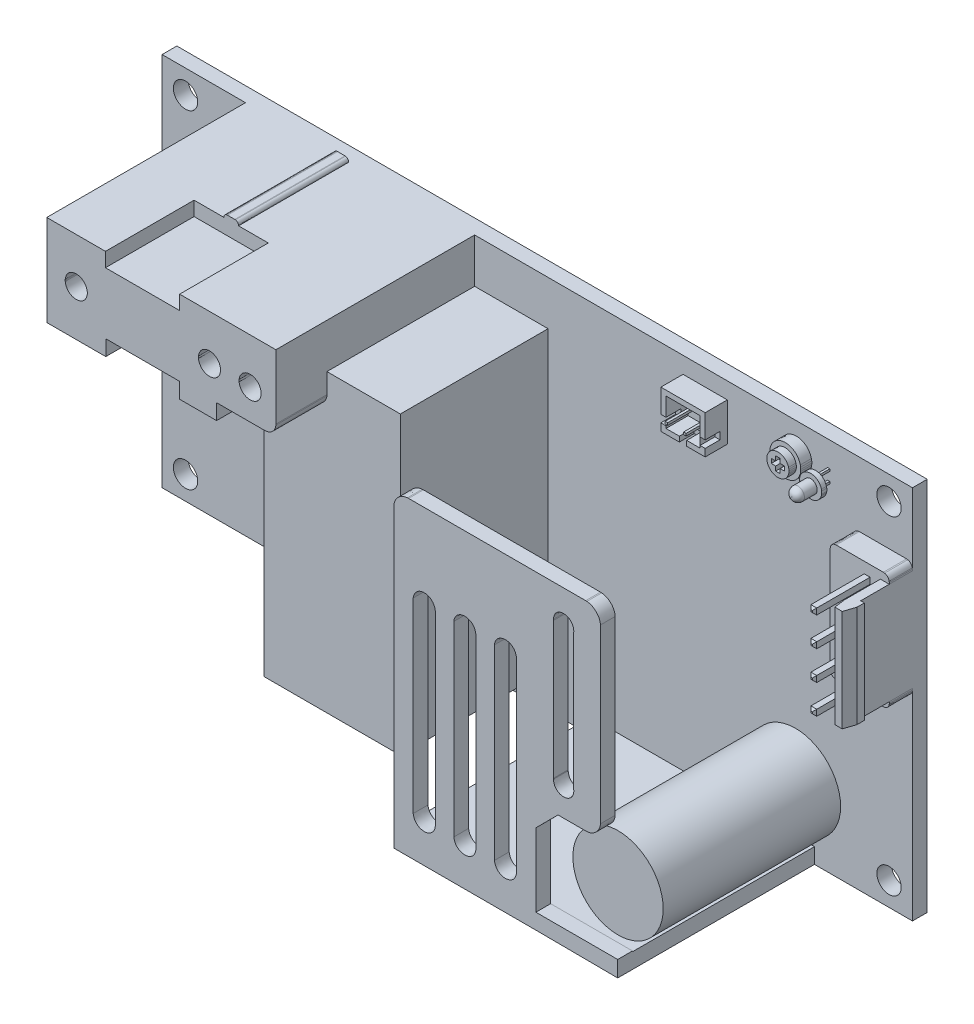
SolidWorks part; units mm, degrees
ref_plane "Спереди" through (0, 0, 0) normal (0, 0, 1) x (1, 0, 0)
ref_plane "Сверху" through (0, 0, 0) normal (0, 1, 0) x (1, 0, 0)
ref_plane "Справа" through (0, 0, 0) normal (1, 0, 0) x (0, 0, -1)
sketch "Model" plane through (0, 0, 0) normal (0, 0, 1) x (1, 0, 0)
  line L13 (0, 0) -> (101.6, 0)
  line L14 (0, 0) -> (0, 50.8)
  line L15 (0, 50.8) -> (101.6, 50.8)
  line L16 (101.6, 0) -> (101.6, 50.8)
  circle A5 centre (3.175, 47.625) radius 1.65
  circle A6 centre (3.175, 3.175) radius 1.65
  circle A7 centre (98.425, 3.175) radius 1.65
  circle A8 centre (98.425, 47.625) radius 1.65
  spline S9 degree 3 poles (101.6, 0.0137) (101.6, 0.0091) (101.6, 0.0046) (101.6, 0) knots 0 0 0 0 1 1 1 1 weights 1 1 1 1
  dimension "D1" = 101.6
  dimension "D3" = 3.175
  dimension "D4" = 44.45
  dimension "D5" = 3.175
  dimension "D6" = 95.25
  dimension "D7" = 3.3
  dimension "D2" = 50.8
extrude "Текстолит" add sketch "Model" against normal blind 2 contours L13 L16 L15 L14 A8 A7 A6 A5 region at (50.8, 25.4, 0)
sketch "Sketch2" plane through (0, 0, 0) normal (0, 0, 1) x (1, 0, 0)
  line L0 (0.0004, 28.8168) -> (1.197, 28.8168)
  line L1 (1.197, 28.8168) -> (1.197, 38.6355)
  line L2 (1.197, 38.6355) -> (0.0004, 38.6355)
  line L3 (0.0004, 38.6355) -> (0.0004, 38.8258)
  line L12 (0.0004, 28.8168) -> (0.0004, 28.6265)
  spline S0 degree 3 poles (7.1943, 27.8241) (7.2487, 27.8287) (7.3032, 27.8332) (7.3576, 27.8378) knots 15 15 15 15 16 16 16 16 weights 1 1 1 1
  spline S1 degree 3 poles (0.8028, 27.8241) (2.9333, 27.8241) (5.0638, 27.8241) (7.1943, 27.8241) knots 14 14 14 14 15 15 15 15 weights 1 1 1 1
  spline S2 degree 3 poles (0.6395, 27.8378) (0.6939, 27.8332) (0.7484, 27.8287) (0.8028, 27.8241) knots 13 13 13 13 14 14 14 14 weights 1 1 1 1
  spline S3 degree 3 poles (0.0141, 28.4632) (0.0547, 28.1742) (0.3505, 27.8784) (0.6395, 27.8378) knots 12 12 12 12 13 13 13 13 weights 1 1 1 1
  spline S4 degree 3 poles (0.0004, 28.6265) (0.0049, 28.5721) (0.0095, 28.5177) (0.0141, 28.4632) knots 11 11 11 11 12 12 12 12 weights 1 1 1 1
  spline S6 degree 3 poles (0.0141, 38.9891) (0.0095, 38.9346) (0.0049, 38.8802) (0.0004, 38.8258) knots 9 9 9 9 10 10 10 10 weights 1 1 1 1
  spline S7 degree 3 poles (0.6395, 39.6145) (0.3505, 39.5739) (0.0547, 39.2781) (0.0141, 38.9891) knots 8 8 8 8 9 9 9 9 weights 1 1 1 1
  spline S8 degree 3 poles (0.8028, 39.6282) (0.7484, 39.6236) (0.6939, 39.6191) (0.6395, 39.6145) knots 7 7 7 7 8 8 8 8 weights 1 1 1 1
  spline S9 degree 3 poles (7.1943, 39.6282) (5.0638, 39.6282) (2.9333, 39.6282) (0.8028, 39.6282) knots 6 6 6 6 7 7 7 7 weights 1 1 1 1
  spline S10 degree 3 poles (7.3576, 39.6145) (7.3032, 39.6191) (7.2487, 39.6236) (7.1943, 39.6282) knots 5 5 5 5 6 6 6 6 weights 1 1 1 1
  spline S11 degree 3 poles (7.9831, 38.9891) (7.942, 39.2777) (7.6466, 39.5743) (7.3576, 39.6145) knots 4 4 4 4 5 5 5 5 weights 1 1 1 1
  spline S12 degree 3 poles (7.9967, 38.8258) (7.9922, 38.8802) (7.9876, 38.9346) (7.9831, 38.9891) knots 3 3 3 3 4 4 4 4 weights 1 1 1 1
  spline S13 degree 3 poles (7.9967, 28.6265) (7.9967, 32.0263) (7.9967, 35.426) (7.9967, 38.8258) knots 2 2 2 2 3 3 3 3 weights 1 1 1 1
  spline S14 degree 3 poles (7.9831, 28.4632) (7.9876, 28.5177) (7.9922, 28.5721) (7.9967, 28.6265) knots 1 1 1 1 2 2 2 2 weights 1 1 1 1
  spline S15 degree 3 poles (7.3576, 27.8378) (7.6466, 27.8784) (7.942, 28.1742) (7.9831, 28.4632) knots 0 0 0 0 1 1 1 1 weights 1 1 1 1
sketch "Sketch3" plane through (0, 0, 0) normal (0, 0, 1) x (1, 0, 0)
  spline S0 degree 3 poles (13.6215, 24.7504) (13.617, 24.7504) (13.6124, 24.7504) (13.6079, 24.7504) (12.1121, 24.7504) (10.6162, 24.7504) (9.1204, 24.7504) knots 10 10 10 10 11 11 11 12 12 12 12 weights 1 1 1 1 1 1 1
  spline S1 degree 3 poles (13.6215, 33.2636) (13.6215, 33.2546) (13.6215, 33.2456) (13.6215, 33.2367) (13.6215, 30.4125) (13.6215, 27.5883) (13.6215, 24.7641) (13.6215, 24.7595) (13.6215, 24.755) (13.6215, 24.7504) knots 7 7 7 7 8 8 8 9 9 9 10 10 10 10 weights 1 1 1 1 1 1 1 1 1 1
  spline S2 degree 3 poles (9.1067, 33.2636) (9.1113, 33.2636) (9.1158, 33.2636) (9.1204, 33.2636) (10.6162, 33.2636) (12.1121, 33.2636) (13.6079, 33.2636) (13.6124, 33.2636) (13.617, 33.2636) (13.6215, 33.2636) knots 4 4 4 4 5 5 5 6 6 6 7 7 7 7 weights 1 1 1 1 1 1 1 1 1 1
  spline S3 degree 3 poles (9.1067, 24.7504) (9.1067, 24.755) (9.1067, 24.7595) (9.1067, 24.7641) (9.1067, 27.5883) (9.1067, 30.4125) (9.1067, 33.2367) (9.1067, 33.2456) (9.1067, 33.2546) (9.1067, 33.2636) knots 1 1 1 1 2 2 2 3 3 3 4 4 4 4 weights 1 1 1 1 1 1 1 1 1 1
  spline S4 degree 3 poles (9.1204, 24.7504) (9.1158, 24.7504) (9.1113, 24.7504) (9.1067, 24.7504) knots 0 0 0 0 1 1 1 1 weights 1 1 1 1
  spline S5 degree 3 poles (0.2313, 22.6162) (0.2399, 22.6162) (0.2489, 22.6162) (0.2578, 22.6162) (3.082, 22.6162) (5.9062, 22.6162) (8.7304, 22.6162) (8.735, 22.6162) (8.7395, 22.6162) (8.7444, 22.6162) knots 0 0 0 0 1 1 1 2 2 2 3 3 3 3 weights 1 1 1 1 1 1 1 1 1 1
  spline S6 degree 3 poles (8.7444, 27.1307) (8.7444, 27.1261) (8.7444, 27.1216) (8.7444, 27.117) (8.7444, 25.6212) (8.7444, 24.1254) (8.7444, 22.6295) (8.7444, 22.625) (8.7444, 22.6204) (8.7444, 22.6162) knots 6 6 6 6 7 7 7 8 8 8 9 9 9 9 weights 1 1 1 1 1 1 1 1 1 1
  spline S7 degree 3 poles (0.2313, 27.1307) (0.2403, 27.1307) (0.2492, 27.1307) (0.2582, 27.1307) (3.0824, 27.1307) (5.9066, 27.1307) (8.7308, 27.1307) (8.7353, 27.1307) (8.7399, 27.1307) (8.7444, 27.1307) knots 3 3 3 3 4 4 4 5 5 5 6 6 6 6 weights 1 1 1 1 1 1 1 1 1 1
  spline S8 degree 3 poles (0.2313, 22.6162) (0.2313, 22.6204) (0.2313, 22.625) (0.2313, 22.6295) (0.2313, 24.1254) (0.2313, 25.6212) (0.2313, 27.117) (0.2313, 27.1216) (0.2313, 27.1261) (0.2313, 27.1307) knots 0 0 0 0 1 1 1 2 2 2 3 3 3 3 weights 1 1 1 1 1 1 1 1 1 1
sketch "Sketch4" plane through (0, 0, 0) normal (0, 0, 1) x (1, 0, 0)
  line L0 (42.3183, 42.0829) -> (42.3183, 48.7752)
  line L1 (42.3183, 48.7752) -> (42.3183, 48.8758)
  line L2 (42.3183, 48.8758) -> (42.3183, 50.8)
  line L3 (11.295, 50.8) -> (11.295, 40.5823)
  line L5 (11.295, 50.8) -> (19.2847, 50.8)
  line L6 (0, 50.8) -> (101.6, 50.8) construction
  line L7 (11.2952, 40.4746) -> (11.295, 40.5823)
  line L8 (11.2952, 40.4746) -> (11.2952, 38.4749)
  line L9 (11.2952, 38.4749) -> (12.2902, 38.4749)
  line L10 (12.2902, 38.4749) -> (29.2842, 38.4749)
  line L11 (25.2637, 50.8) -> (42.3183, 50.8)
  line L12 (19.2847, 50.8) -> (23.2639, 50.8)
  line L14 (29.2842, 38.4749) -> (33.2841, 38.4749)
  line L15 (33.2841, 38.4749) -> (34.2889, 38.4749)
  line L16 (34.2889, 38.4749) -> (34.2889, 40.4746)
  line L17 (34.2889, 40.4746) -> (34.2889, 40.5753)
  line L18 (34.2889, 40.5753) -> (40.8213, 40.5753)
  line L24 (23.7663, 51.3024) -> (24.7612, 51.3024)
  line L30 (40.8213, 40.5753) -> (40.9619, 40.5851)
  line L31 (42.3187, 41.942) -> (42.3183, 42.0829)
  arc A0 (40.9619, 40.5851) -> (42.3187, 41.942) centre (40.8198, 42.084) ccw
  spline S0 degree 3 poles (23.2738, 50.8805) (23.2705, 50.8537) (23.2672, 50.8268) (23.2639, 50.8) knots 2 2 2 2 3 3 3 3 weights 1 1 1 1
  spline S1 degree 3 poles (23.6862, 51.2925) (23.4997, 51.2994) (23.2669, 51.0673) (23.2738, 50.8805) knots 1 1 1 1 2 2 2 2 weights 1 1 1 1
  spline S2 degree 3 poles (23.7663, 51.3024) (23.7396, 51.2994) (23.7129, 51.296) (23.6862, 51.2925) knots 0 0 0 0 1 1 1 1 weights 1 1 1 1
  spline S3 degree 3 poles (24.8418, 51.2925) (24.8149, 51.296) (24.7881, 51.2994) (24.7612, 51.3024) knots 2 2 2 2 3 3 3 3 weights 1 1 1 1
  spline S4 degree 3 poles (25.2538, 50.8805) (25.2261, 51.0761) (25.0464, 51.2906) (24.8418, 51.2925) knots 1 1 1 1 2 2 2 2 weights 1 1 1 1
  spline S5 degree 3 poles (25.2637, 50.8) (25.2604, 50.8268) (25.2571, 50.8537) (25.2538, 50.8805) knots 0 0 0 0 1 1 1 1 weights 1 1 1 1
  spline S6 degree 3 poles (37.3341, 44.8159) (37.3341, 44.7691) (37.3341, 44.7222) (37.3341, 44.6754) (37.3341, 44.6319) (37.3341, 44.5883) (37.3341, 44.5448) knots 4 4 4 4 5 5 5 6 6 6 6 weights 1 1 1 1 1 1 1
  spline S7 degree 3 poles (40.3189, 44.8159) (40.0873, 46.6281) (37.581, 46.633) (37.3341, 44.8159) knots 3 3 3 3 4 4 4 4 weights 1 1 1 1
  spline S8 degree 3 poles (40.3288, 44.6754) (40.3255, 44.7222) (40.3222, 44.7691) (40.3189, 44.8159) knots 2 2 2 2 3 3 3 3 weights 1 1 1 1
  spline S9 degree 3 poles (40.3189, 44.5448) (40.3222, 44.5883) (40.3255, 44.6319) (40.3288, 44.6754) knots 1 1 1 1 2 2 2 2 weights 1 1 1 1
  spline S10 degree 3 poles (37.3341, 44.5448) (37.5658, 42.7307) (40.0983, 42.7288) (40.3189, 44.5448) knots 0 0 0 0 1 1 1 1 weights 1 1 1 1
  spline S11 degree 3 poles (13.7875, 44.6754) (13.7908, 44.6319) (13.7941, 44.5883) (13.7974, 44.5448) knots 5 5 5 5 6 6 6 6 weights 1 1 1 1
  spline S12 degree 3 poles (13.7974, 44.8159) (13.7941, 44.7691) (13.7908, 44.7222) (13.7875, 44.6754) knots 4 4 4 4 5 5 5 5 weights 1 1 1 1
  spline S13 degree 3 poles (16.7826, 44.8159) (16.5365, 46.6311) (14.0309, 46.6303) (13.7974, 44.8159) knots 3 3 3 3 4 4 4 4 weights 1 1 1 1
  spline S14 degree 3 poles (16.7826, 44.5448) (16.7826, 44.5883) (16.7826, 44.6319) (16.7826, 44.6754) (16.7826, 44.7222) (16.7826, 44.7691) (16.7826, 44.8159) knots 1 1 1 1 2 2 2 3 3 3 3 weights 1 1 1 1 1 1 1
  spline S15 degree 3 poles (13.7974, 44.5448) (14.0184, 42.7288) (16.5505, 42.7307) (16.7826, 44.5448) knots 0 0 0 0 1 1 1 1 weights 1 1 1 1
  spline S16 degree 3 poles (31.8369, 44.8159) (31.8369, 44.7691) (31.8369, 44.7222) (31.8369, 44.6754) (31.8369, 44.6319) (31.8369, 44.5883) (31.8369, 44.5448) knots 4 4 4 4 5 5 5 6 6 6 6 weights 1 1 1 1 1 1 1
  spline S17 degree 3 poles (34.8217, 44.8159) (34.5893, 46.6292) (32.083, 46.6322) (31.8369, 44.8159) knots 3 3 3 3 4 4 4 4 weights 1 1 1 1
  spline S18 degree 3 poles (34.8316, 44.6754) (34.8283, 44.7222) (34.825, 44.7691) (34.8217, 44.8159) knots 2 2 2 2 3 3 3 3 weights 1 1 1 1
  spline S19 degree 3 poles (34.8217, 44.5448) (34.825, 44.5883) (34.8283, 44.6319) (34.8316, 44.6754) knots 1 1 1 1 2 2 2 2 weights 1 1 1 1
  spline S20 degree 3 poles (31.8369, 44.5448) (32.0685, 42.7307) (34.6011, 42.7288) (34.8217, 44.5448) knots 0 0 0 0 1 1 1 1 weights 1 1 1 1
  point P52 (24.2638, 50.8)
sketch "Sketch5" plane through (0, 0, 0) normal (0, 0, 1) x (1, 0, 0)
  line L0 (33.7672, 4.7598) -> (33.7865, 4.8384)
  line L5 (33.7865, 38.4749) -> (36.2891, 40.5753)
  line L6 (42.3187, 44.7825) -> (36.2891, 40.5753)
  spline S0 degree 3 poles (52.2616, 4.7598) (52.2616, 4.7647) (52.2616, 4.7693) (52.2616, 4.7738) (52.2616, 18.1056) (52.2616, 31.4374) (52.2616, 44.7692) (52.2616, 44.7738) (52.2616, 44.7783) (52.2616, 44.7825) knots 0 0 0 0 1 1 1 2 2 2 3 3 3 3 weights 1 1 1 1 1 1 1 1 1 1
  spline S1 degree 3 poles (42.3187, 44.7825) (42.9246, 44.7825) (43.5306, 44.7825) (44.1365, 44.7825) (46.8403, 44.7825) (49.5445, 44.7825) (52.2487, 44.7825) (52.2531, 44.7825) (52.2576, 44.7825) (52.2616, 44.7825) knots 0 0 0 0 1 1 1 2 2 2 3 3 3 3 weights 1 1 1 1 1 1 1 1 1 1
  spline S2 degree 3 poles (33.7672, 4.7598) (33.7717, 4.7598) (33.7763, 4.7598) (33.7808, 4.7598) (39.9365, 4.7598) (46.0926, 4.7598) (52.2483, 4.7598) (52.2529, 4.7598) (52.2574, 4.7598) (52.2616, 4.7598) knots 0 0 0 0 1 1 1 2 2 2 3 3 3 3 weights 1 1 1 1 1 1 1 1 1 1
  spline S5 degree 3 poles (33.7865, 38.4749) (33.7865, 38.2539) (33.7865, 38.0329) (33.7865, 37.8118) (33.7865, 26.8239) (33.7865, 15.8362) (33.7865, 4.8486) (33.7865, 4.8452) (33.7865, 4.8418) (33.7865, 4.8384) knots 3 3 3 3 4 4 4 5 5 5 6 6 6 6 weights 1 1 1 1 1 1 1 1 1 1
  spline S6 degree 3 poles (33.7865, 4.8384) (33.7865, 4.8417) (33.7865, 4.8449) (33.7865, 4.8482) (33.7865, 15.8093) (33.7865, 26.7703) (33.7865, 37.7313) (33.7865, 37.9792) (33.7865, 38.227) (33.7865, 38.4749) knots 0 0 0 0 1 1 1 2 2 2 3 3 3 3 weights 1 1 1 1 1 1 1 1 1 1
sketch "Sketch6" plane through (0, 0, 0) normal (0, 0, 1) x (1, 0, 0)
  line L0 (70.5328, 48.5697) -> (76.5302, 48.5697)
  line L1 (76.5302, 48.5697) -> (76.5302, 43.3748)
  line L2 (70.5328, 43.3748) -> (73.035, 43.3752)
  line L3 (70.5328, 43.3748) -> (70.5328, 48.5697)
  line L4 (73.035, 44.0686) -> (74.028, 44.0686)
  line L5 (73.035, 44.0686) -> (71.2266, 44.0686)
  line L6 (71.2266, 44.0686) -> (71.2266, 47.8763)
  line L7 (71.2266, 47.8763) -> (72.5318, 47.8763)
  line L8 (72.5318, 47.8763) -> (75.8364, 47.8763)
  line L9 (75.8364, 47.8763) -> (75.8364, 44.0686)
  line L10 (75.8364, 44.0686) -> (74.028, 44.0686)
  line L11 (74.028, 43.3752) -> (73.035, 43.3752)
  line L12 (74.028, 43.3752) -> (76.5302, 43.3748)
sketch "Sketch8" plane through (0, 0, 0) normal (0, 0, 1) x (1, 0, 0)
  spline S0 degree 3 poles (91.7546, 46.3463) (91.7409, 46.2828) (91.7273, 46.2192) (91.7136, 46.1557) knots 7 7 7 7 8 8 8 8 weights 1 1 1 1
  spline S1 degree 3 poles (91.7546, 46.7268) (91.7546, 46.6634) (91.7546, 46.6) (91.7546, 46.5366) (91.7546, 46.4731) (91.7546, 46.4097) (91.7546, 46.3463) knots 5 5 5 5 6 6 6 7 7 7 7 weights 1 1 1 1 1 1 1
  spline S2 degree 3 poles (91.7136, 46.9038) (91.7273, 46.8448) (91.7409, 46.7858) (91.7546, 46.7268) knots 4 4 4 4 5 5 5 5 weights 1 1 1 1
  spline S3 degree 3 poles (88.8173, 46.9854) (89.3394, 48.4296) (91.2974, 48.3685) (91.7136, 46.9038) knots 3 3 3 3 4 4 4 4 weights 1 1 1 1
  spline S4 degree 3 poles (88.7763, 46.7952) (88.7899, 46.8586) (88.8036, 46.922) (88.8173, 46.9854) knots 2 2 2 2 3 3 3 3 weights 1 1 1 1
  spline S5 degree 3 poles (88.7626, 46.6182) (88.7671, 46.6772) (88.7717, 46.7362) (88.7763, 46.7952) knots 1 1 1 1 2 2 2 2 weights 1 1 1 1
  spline S6 degree 3 poles (91.7136, 46.1557) (91.1808, 44.3944) (88.7083, 44.8284) (88.7626, 46.6182) knots 0 0 0 0 1 1 1 1 weights 1 1 1 1
sketch "Sketch9" plane through (0, 0, 0) normal (0, 0, 1) x (1, 0, 0)
  line L0 (101.6, 27.2799) -> (100.4033, 27.2799)
  line L1 (100.4033, 27.2799) -> (100.4033, 41.056)
  line L2 (100.4033, 41.056) -> (101.6, 41.056)
  line L3 (101.6003, 27.0897) -> (101.6, 27.2799)
  line L20 (101.6, 41.056) -> (101.6003, 41.26)
  spline S0 degree 3 poles (94.2431, 26.3009) (94.2975, 26.2964) (94.352, 26.2918) (94.406, 26.2873) knots 3 3 3 3 4 4 4 4 weights 1 1 1 1
  spline S1 degree 3 poles (93.6177, 26.9264) (93.6587, 26.637) (93.9537, 26.3416) (94.2431, 26.3009) knots 2 2 2 2 3 3 3 3 weights 1 1 1 1
  spline S2 degree 3 poles (93.604, 27.0897) (93.6085, 27.0352) (93.6131, 26.9808) (93.6177, 26.9264) knots 1 1 1 1 2 2 2 2 weights 1 1 1 1
  spline S3 degree 3 poles (93.604, 41.26) (93.604, 36.5368) (93.604, 31.8132) (93.604, 27.0897) knots 0 0 0 0 1 1 1 1 weights 1 1 1 1
  spline S4 degree 3 poles (93.6177, 41.4096) (93.6131, 41.3597) (93.6085, 41.3098) (93.604, 41.26) knots 3 3 3 3 4 4 4 4 weights 1 1 1 1
  spline S5 degree 3 poles (94.2435, 42.0354) (93.9431, 42.0054) (93.661, 41.6898) (93.6177, 41.4096) knots 2 2 2 2 3 3 3 3 weights 1 1 1 1
  spline S6 degree 3 poles (94.4064, 42.0624) (94.3521, 42.0534) (94.2978, 42.0444) (94.2435, 42.0354) knots 1 1 1 1 2 2 2 2 weights 1 1 1 1
  spline S7 degree 3 poles (100.7979, 42.0624) (98.6677, 42.0624) (96.537, 42.0624) (94.4064, 42.0624) knots 0 0 0 0 1 1 1 1 weights 1 1 1 1
  spline S8 degree 3 poles (100.9612, 42.035) (100.9068, 42.0441) (100.8524, 42.0533) (100.7979, 42.0624) knots 3 3 3 3 4 4 4 4 weights 1 1 1 1
  spline S9 degree 3 poles (101.5867, 41.4096) (101.5445, 41.6891) (101.2608, 42.0058) (100.9612, 42.035) knots 2 2 2 2 3 3 3 3 weights 1 1 1 1
  spline S10 degree 3 poles (101.6003, 41.26) (101.5958, 41.3098) (101.5912, 41.3597) (101.5867, 41.4096) knots 1 1 1 1 2 2 2 2 weights 1 1 1 1
  spline S12 degree 3 poles (101.5867, 26.9264) (101.5912, 26.9808) (101.5958, 27.0352) (101.6003, 27.0897) knots 3 3 3 3 4 4 4 4 weights 1 1 1 1
  spline S13 degree 3 poles (100.9612, 26.3009) (101.2498, 26.3416) (101.546, 26.6374) (101.5867, 26.9264) knots 2 2 2 2 3 3 3 3 weights 1 1 1 1
  spline S14 degree 3 poles (100.7979, 26.2873) (100.8524, 26.2918) (100.9068, 26.2964) (100.9612, 26.3009) knots 1 1 1 1 2 2 2 2 weights 1 1 1 1
  spline S15 degree 3 poles (94.406, 26.2873) (96.5367, 26.2873) (98.6673, 26.2873) (100.7979, 26.2873) knots 0 0 0 0 1 1 1 1 weights 1 1 1 1
sketch "Sketch10" plane through (0, 0, 0) normal (0, 0, 1) x (1, 0, 0)
  circle A0 centre (85.7534, 8.5646) radius 6.1168
sketch "Sketch12" plane through (0, 0, 0) normal (0, 0, 1) x (1, 0, 0)
  line L0 (66.1368, 30.5761) -> (66.1368, 5.5823)
  line L1 (83.9949, 15.0783) -> (80.2464, 15.0783)
  line L2 (80.2464, 15.0783) -> (77.2517, 12.0729)
  line L3 (60.0165, 42.0817) -> (83.9949, 42.0817)
  line L4 (74.6288, 5.5804) -> (74.6288, 30.5746)
  line L5 (79.6335, 37.5794) -> (79.6335, 19.0774)
  line L6 (69.1315, 5.5808) -> (69.1315, 30.5746)
  line L7 (71.6337, 30.5746) -> (71.6337, 5.5804)
  line L8 (85.995, 40.082) -> (85.995, 17.078)
  line L9 (77.2517, 2.1741) -> (77.2517, 12.0729)
  line L11 (77.2517, 0.0737) -> (58.0167, 0.0752)
  line L12 (59.8558, 42.073) -> (60.0165, 42.0817)
  line L13 (83.9949, 42.0817) -> (84.1559, 42.0715)
  line L14 (85.995, 40.2324) -> (85.995, 40.082)
  line L15 (85.995, 17.078) -> (85.995, 16.9166)
  line L16 (84.1555, 15.0874) -> (83.9949, 15.0783)
  line L17 (66.1368, 5.4403) -> (66.1368, 5.5823)
  line L18 (69.1217, 5.4403) -> (69.1315, 5.5808)
  line L19 (66.1368, 30.7151) -> (66.1368, 30.5761)
  line L20 (69.1217, 30.7151) -> (69.1315, 30.5746)
  line L21 (77.2517, 2.1741) -> (88.3281, 2.1741)
  line L22 (88.3281, 2.1741) -> (88.3281, 0)
  line L23 (0, 0) -> (101.6, 0) construction
  line L24 (88.3281, 0) -> (77.2517, 0.0737)
  spline S0 degree 3 poles (60.6396, 30.7166) (60.6396, 30.6698) (60.6396, 30.623) (60.6396, 30.5761) (60.6396, 22.2449) (60.6396, 13.9136) (60.6396, 5.5823) (60.6396, 5.5355) (60.6396, 5.4886) (60.6396, 5.4418) knots 5 5 5 5 6 6 6 7 7 7 8 8 8 8 weights 1 1 1 1 1 1 1 1 1 1
  spline S1 degree 3 poles (63.6343, 30.7166) (63.3814, 32.5292) (60.8906, 32.533) (60.6396, 30.7166) knots 4 4 4 4 5 5 5 5 weights 1 1 1 1
  spline S2 degree 3 poles (63.6343, 5.4418) (63.6343, 5.4886) (63.6343, 5.5355) (63.6343, 5.5823) (63.6343, 13.9136) (63.6343, 22.2449) (63.6343, 30.5761) (63.6343, 30.623) (63.6343, 30.6698) (63.6343, 30.7166) knots 1 1 1 1 2 2 2 3 3 3 4 4 4 4 weights 1 1 1 1 1 1 1 1 1 1
  spline S3 degree 3 poles (60.6396, 5.4418) (60.8868, 3.6251) (63.386, 3.6292) (63.6343, 5.4418) knots 0 0 0 0 1 1 1 1 weights 1 1 1 1
  spline S4 degree 3 poles (58.0167, 40.2339) (58.0167, 40.1836) (58.0167, 40.1334) (58.0167, 40.0831) (58.0167, 27.4473) (58.0167, 14.8114) (58.0167, 2.1756) (58.0167, 2.1422) (58.0167, 2.1087) (58.0167, 2.0753) (58.0167, 1.4086) (58.0167, 0.7419) (58.0167, 0.0752) knots 2 2 2 2 3 3 3 4 4 4 5 5 5 6 6 6 6 weights 1 1 1 1 1 1 1 1 1 1 1 1 1
  spline S5 degree 3 poles (59.8558, 42.073) (58.8916, 42.0103) (58.0801, 41.1977) (58.0167, 40.2339) knots 1 1 1 1 2 2 2 2 weights 1 1 1 1
  spline S9 degree 3 poles (66.1368, 5.4403) (66.3598, 3.6308) (68.9109, 3.6296) (69.1217, 5.4403) knots 1 1 1 1 2 2 2 2 weights 1 1 1 1
  spline S12 degree 3 poles (69.1217, 30.7151) (68.9079, 32.5254) (66.362, 32.5235) (66.1368, 30.7151) knots 1 1 1 1 2 2 2 2 weights 1 1 1 1
  spline S14 degree 3 poles (71.6337, 30.7151) (71.6337, 30.6683) (71.6337, 30.6215) (71.6337, 30.5746) knots 2 2 2 2 3 3 3 3 weights 1 1 1 1
  spline S15 degree 3 poles (74.6189, 30.7151) (74.4047, 32.5254) (71.8596, 32.5239) (71.6337, 30.7151) knots 1 1 1 1 2 2 2 2 weights 1 1 1 1
  spline S16 degree 3 poles (74.6288, 30.5746) (74.6255, 30.6215) (74.6222, 30.6683) (74.6189, 30.7151) knots 0 0 0 0 1 1 1 1 weights 1 1 1 1
  spline S17 degree 3 poles (79.6236, 37.7097) (79.627, 37.6662) (79.6304, 37.6226) (79.6335, 37.5794) knots 3 3 3 3 4 4 4 4 weights 1 1 1 1
  spline S18 degree 3 poles (82.3874, 37.7097) (82.2765, 39.5359) (79.7333, 39.5291) (79.6236, 37.7097) knots 2 2 2 2 3 3 3 3 weights 1 1 1 1
  spline S19 degree 3 poles (82.3771, 37.5791) (82.3805, 37.6226) (82.384, 37.6662) (82.3874, 37.7097) knots 1 1 1 1 2 2 2 2 weights 1 1 1 1
  spline S20 degree 3 poles (82.3768, 19.0774) (82.3771, 25.2449) (82.3771, 31.412) (82.3771, 37.5791) knots 0 0 0 0 1 1 1 1 weights 1 1 1 1
  spline S22 degree 3 poles (85.995, 40.2324) (85.9361, 41.1886) (85.114, 42.016) (84.1559, 42.0715) knots 1 1 1 1 2 2 2 2 weights 1 1 1 1
  spline S24 degree 3 poles (82.387, 18.9467) (82.3836, 18.9903) (82.3802, 19.0338) (82.3768, 19.0774) knots 2 2 2 2 3 3 3 3 weights 1 1 1 1
  spline S25 degree 3 poles (79.6232, 18.9467) (79.7333, 17.1274) (82.2761, 17.1205) (82.387, 18.9467) knots 1 1 1 1 2 2 2 2 weights 1 1 1 1
  spline S26 degree 3 poles (79.6335, 19.0774) (79.63, 19.0338) (79.6266, 18.9903) (79.6232, 18.9467) knots 0 0 0 0 1 1 1 1 weights 1 1 1 1
  spline S28 degree 3 poles (84.1555, 15.0874) (85.1128, 15.1341) (85.9289, 15.9657) (85.995, 16.9166) knots 1 1 1 1 2 2 2 2 weights 1 1 1 1
  spline S30 degree 3 poles (74.6185, 5.4399) (74.6219, 5.4867) (74.6253, 5.5336) (74.6288, 5.5804) knots 2 2 2 2 3 3 3 3 weights 1 1 1 1
  spline S31 degree 3 poles (71.6337, 5.4399) (71.8574, 3.63) (74.4074, 3.6292) (74.6185, 5.4399) knots 1 1 1 1 2 2 2 2 weights 1 1 1 1
  spline S32 degree 3 poles (71.6337, 5.5804) (71.6337, 5.5336) (71.6337, 5.4867) (71.6337, 5.4399) knots 0 0 0 0 1 1 1 1 weights 1 1 1 1
extrude "Предохранители" add sketch "Sketch3" along normal blind 8
sketch "Sketch13" plane through (0, 0, 0) normal (0, 0, 1) x (1, 0, 0)
  spline S0 degree 3 poles (87.9602, 47.1491) (87.9466, 47.2306) (87.9331, 47.3121) (87.9195, 47.3936) knots 7 7 7 7 8 8 8 8 weights 1 1 1 1
  spline S1 degree 3 poles (87.9739, 46.8905) (87.9693, 46.9767) (87.9647, 47.0629) (87.9602, 47.1491) knots 6 6 6 6 7 7 7 7 weights 1 1 1 1
  spline S2 degree 3 poles (87.9602, 46.6459) (87.9647, 46.7274) (87.9693, 46.809) (87.9739, 46.8905) knots 5 5 5 5 6 6 6 6 weights 1 1 1 1
  spline S3 degree 3 poles (87.9195, 46.3873) (87.9331, 46.4735) (87.9466, 46.5597) (87.9602, 46.6459) knots 4 4 4 4 5 5 5 5 weights 1 1 1 1
  spline S4 degree 3 poles (83.7989, 46.6459) (84.1061, 44.3276) (87.3154, 44.1331) (87.9195, 46.3873) knots 3 3 3 3 4 4 4 4 weights 1 1 1 1
  spline S5 degree 3 poles (83.7852, 46.8905) (83.7898, 46.809) (83.7943, 46.7274) (83.7989, 46.6459) knots 2 2 2 2 3 3 3 3 weights 1 1 1 1
  spline S6 degree 3 poles (83.7989, 47.1491) (83.7943, 47.0629) (83.7898, 46.9767) (83.7852, 46.8905) knots 1 1 1 1 2 2 2 2 weights 1 1 1 1
  spline S7 degree 3 poles (87.9195, 47.3936) (87.2983, 49.6558) (84.1411, 49.469) (83.7989, 47.1491) knots 0 0 0 0 1 1 1 1 weights 1 1 1 1
extrude "подстройка няпряжения-1" add sketch "Sketch13" along normal blind 1.5
sketch "Sketch7" plane through (0, 0, 0) normal (0, 0, 1) x (1, 0, 0)
  line L0 (85.5807, 47.7878) -> (85.5807, 47.1893)
  line L1 (85.5807, 47.1893) -> (84.9822, 47.1893)
  line L2 (84.9822, 47.1893) -> (84.9822, 46.5912)
  line L3 (84.9822, 46.5912) -> (85.5807, 46.5912)
  line L4 (85.5807, 46.5912) -> (85.5807, 45.9928)
  line L5 (85.5807, 45.9928) -> (86.1792, 45.9928)
  line L6 (86.1792, 45.9928) -> (86.1792, 46.5912)
  line L7 (86.1792, 46.5912) -> (86.7773, 46.5912)
  line L8 (86.7773, 46.5912) -> (86.7773, 47.1893)
  line L9 (86.7773, 47.1893) -> (86.1792, 47.1893)
  line L10 (86.1792, 47.1893) -> (86.1792, 47.7878)
  line L11 (86.1792, 47.7878) -> (85.5807, 47.7878)
  spline S8 degree 3 poles (87.3621, 47.1081) (87.3485, 47.176) (87.335, 47.244) (87.3214, 47.312) knots 7 7 7 7 8 8 8 8 weights 1 1 1 1
  spline S9 degree 3 poles (87.3757, 46.8905) (87.3712, 46.963) (87.3666, 47.0355) (87.3621, 47.1081) knots 6 6 6 6 7 7 7 7 weights 1 1 1 1
  spline S10 degree 3 poles (87.3621, 46.6729) (87.3666, 46.7454) (87.3712, 46.8179) (87.3757, 46.8905) knots 5 5 5 5 6 6 6 6 weights 1 1 1 1
  spline S11 degree 3 poles (87.3214, 46.469) (87.335, 46.5369) (87.3485, 46.6049) (87.3621, 46.6729) knots 4 4 4 4 5 5 5 5 weights 1 1 1 1
  spline S12 degree 3 poles (84.3974, 46.6729) (84.6723, 45.081) (86.8206, 44.9317) (87.3214, 46.469) knots 3 3 3 3 4 4 4 4 weights 1 1 1 1
  spline S13 degree 3 poles (84.3841, 46.8905) (84.3885, 46.8179) (84.393, 46.7454) (84.3974, 46.6729) knots 2 2 2 2 3 3 3 3 weights 1 1 1 1
  spline S14 degree 3 poles (84.3974, 47.1081) (84.393, 47.0355) (84.3885, 46.963) (84.3841, 46.8905) knots 1 1 1 1 2 2 2 2 weights 1 1 1 1
  spline S15 degree 3 poles (87.3214, 47.312) (86.8221, 48.8579) (84.6708, 48.7064) (84.3974, 47.1081) knots 0 0 0 0 1 1 1 1 weights 1 1 1 1
extrude "подстройка няпряжения-2" add sketch "Sketch7" along normal blind 2.5
extrude "светодиод-1" add sketch "Sketch8" along normal blind 0.68 from offset 1.76 separate body
sketch "Sketch14" plane through (0, 0, 2.44) normal (0, 0, 1) x (1, 0, 0)
  line L0 (90.2582, 45.0344) -> (90.2582, 48.0387) construction
  line L1 (88.7619, 46.5366) -> (91.7546, 46.5366) construction
  line L2 (91.7546, 46.3463) -> (91.7546, 46.7268) construction
  line L4 (90.1082, 47.4266) -> (90.4082, 47.4266)
  line L5 (90.1082, 47.4266) -> (90.1082, 47.1266)
  line L6 (90.1082, 47.1266) -> (90.4082, 47.1266)
  line L7 (90.4082, 47.4266) -> (90.4082, 47.1266)
  line L8 (90.1082, 47.4266) -> (90.4082, 47.1266) construction
  line L9 (90.1082, 47.1266) -> (90.4082, 47.4266) construction
  line L10 (90.1082, 45.6466) -> (90.4082, 45.6466)
  line L11 (90.1082, 45.6466) -> (90.1082, 45.9466)
  line L12 (90.1082, 45.9466) -> (90.4082, 45.9466)
  line L13 (90.4082, 45.6466) -> (90.4082, 45.9466)
  line L14 (90.1082, 45.6466) -> (90.4082, 45.9466) construction
  line L15 (90.1082, 45.9466) -> (90.4082, 45.6466) construction
  spline S2 degree 3 poles (88.7626, 46.6182) (88.7083, 44.8284) (91.1808, 44.3944) (91.7136, 46.1557) knots 0 0 0 0 1 1 1 1 weights 1 1 1 1 construction
  point P2 (90.2582, 47.2766)
  point P11 (90.2582, 46.5366)
  point P15 (90.2582, 45.7966)
  dimension "D1" = 0.3
  dimension "D2" = 1.48
  dimension "D3" = 0.74
extrude "светодиод-ноги" add sketch "Sketch14" against normal blind 6.02
sketch "Sketch15" plane through (0, 0, 2.44) normal (0, 0, 1) x (1, 0, 0)
  circle A0 centre (90.2582, 46.5366) radius 0.885
  dimension "D1" = 1.77
extrude "светодиод-2" add sketch "Sketch15" along normal blind 2.56
fillet "светодиод-3" radius 0.83 1 edges at (91.1432, 46.5366, 5)
sketch "Sketch16" plane through (0, 0, 0) normal (0, 0, 1) x (1, 0, 0)
  line L0 (2.6043, 38.1525) -> (3.393, 38.1525)
  line L1 (3.393, 38.1525) -> (3.393, 37.3234)
  line L2 (3.393, 37.3234) -> (2.6043, 37.3234)
  line L3 (2.6043, 37.3234) -> (2.6043, 38.1525)
  line L4 (2.6043, 30.122) -> (3.393, 30.122)
  line L5 (3.393, 30.122) -> (3.393, 29.293)
  line L6 (3.393, 29.293) -> (2.6043, 29.293)
  line L7 (2.6043, 29.293) -> (2.6043, 30.122)
extrude "CN1 ввод" add sketch "Sketch2" along normal blind 3.27
extrude "CN1 ноги" add sketch "Sketch16" along normal blind 10.8
sketch "Sketch17" plane through (0, 28.8168, 0) normal (0, 1, 0) x (1, 0, 0)
  line L1 (0, 0) -> (1.2, 0)
  line L2 (0, 0) -> (0, -7)
  line L3 (0, -9.51) -> (1, -9.51)
  line L4 (1.2, 0) -> (1.2, -8)
  line L5 (0, -7) -> (-0.5, -7)
  line L6 (-0.5, -7) -> (-0.5, -8)
  line L7 (-0.5, -8) -> (0, -9.51)
  line L8 (1.2, -8) -> (1, -9.51)
  dimension "D1" = 9.51
  dimension "D2" = 0.5
  dimension "D3" = 7
  dimension "D4" = 8
  dimension "D5" = 1
  dimension "D6" = 0.5
  dimension "D7" = 1.7
extrude "CN1 зацеп" add sketch "Sketch17" along normal up to surface (9.8188 mm away) up to face at (0.5987, 38.6355, 1.635)
chamfer "CN1 ногих45" distance 0.3 angle 45 8 edges at (3.393, 29.7075, 10.8) (2.9987, 30.122, 10.8) (2.6043, 29.7075, 10.8) (2.9987, 29.293, 10.8) (3.393, 37.738, 10.8) (2.9987, 38.1525, 10.8) (2.6043, 37.738, 10.8) (2.9987, 37.3234, 10.8)
sketch "Sketch18" plane through (0, 0, 0) normal (0, 0, 1) x (1, 0, 0)
  line L0 (98.2073, 40.5798) -> (98.9961, 40.5798)
  line L1 (98.9961, 40.5798) -> (98.9961, 39.7509)
  line L2 (98.9961, 39.7509) -> (98.2073, 39.7509)
  line L3 (98.2073, 39.7509) -> (98.2073, 40.5798)
  line L4 (98.2073, 36.6232) -> (98.9961, 36.6232)
  line L5 (98.9961, 36.6232) -> (98.9961, 35.7942)
  line L6 (98.9961, 35.7942) -> (98.2073, 35.7942)
  line L7 (98.2073, 35.7942) -> (98.2073, 36.6232)
  line L8 (98.2073, 32.6663) -> (98.9961, 32.6663)
  line L9 (98.9961, 32.6663) -> (98.9961, 31.8372)
  line L10 (98.9961, 31.8372) -> (98.2073, 31.8372)
  line L11 (98.2073, 31.8372) -> (98.2073, 32.6663)
  line L12 (98.2073, 28.7093) -> (98.9961, 28.7093)
  line L13 (98.9961, 28.7093) -> (98.9961, 27.8803)
  line L14 (98.9961, 27.8803) -> (98.2073, 27.8803)
  line L15 (98.2073, 27.8803) -> (98.2073, 28.7093)
extrude "CN2 вывод" add sketch "Sketch9" along normal blind 3.14
extrude "CN2 ноги" add sketch "Sketch18" along normal blind 10.66
chamfer "CN2 ногих45" distance 0.3 angle 45 16 edges at (98.6017, 28.7093, 10.66) (98.2073, 28.2948, 10.66) (98.6017, 27.8803, 10.66) (98.9961, 28.2948, 10.66) (98.9961, 32.2517, 10.66) (98.6017, 31.8372, 10.66) (98.2073, 32.2517, 10.66) (98.6017, 32.6663, 10.66) (98.2073, 36.2087, 10.66) (98.6017, 35.7942, 10.66) (98.6017, 36.6232, 10.66) (98.9961, 36.2087, 10.66) (98.2073, 40.1654, 10.66) (98.6017, 40.5798, 10.66) (98.9961, 40.1654, 10.66) (98.6017, 39.7509, 10.66)
sketch "Sketch19" plane through (0, 41.056, 0) normal (0, -1, 0) x (1, 0, 0)
  line L0 (101.6, 7.01) -> (102.1, 7.01)
  line L1 (101.6, 0) -> (100.4, 0)
  line L2 (101.6, 0) -> (101.6, 7.01)
  line L3 (101.6, 9.51) -> (100.6, 9.51)
  line L4 (100.4, 0) -> (100.4, 8.01)
  line L5 (102.1, 7.01) -> (102.1, 8.01)
  line L6 (102.1, 8.01) -> (101.6, 9.51)
  line L7 (100.6, 9.51) -> (100.4, 8.01)
  line L8 (100.7979, 0) -> (94.406, 0) construction
  dimension "D1" = 9.51
  dimension "D2" = 1.2
  dimension "D3" = 0.5
  dimension "D4" = 2.5
  dimension "D5" = 1
  dimension "D6" = 1.5
  dimension "D7" = 1
extrude "CN2 зацеп" add sketch "Sketch19" along normal up to surface (13.7761 mm away) up to face at (101.0016, 27.2799, 1.57)
extrude "CN101 ввод" add sketch "Sketch6" along normal blind 3
sketch "Sketch20" plane through (0, 0, 0) normal (0, 0, 1) x (1, 0, 0)
  line L0 (72.4528, 45.5348) -> (72.1186, 45.5348)
  line L1 (72.1186, 45.5348) -> (72.1186, 45.8528)
  line L2 (72.1186, 45.8528) -> (72.4528, 45.8528)
  line L3 (72.4528, 45.8528) -> (72.4528, 45.5348)
  line L4 (74.9496, 45.5348) -> (74.6154, 45.5348)
  line L5 (74.6154, 45.5348) -> (74.6154, 45.8528)
  line L6 (74.6154, 45.8528) -> (74.9496, 45.8528)
  line L7 (74.9496, 45.8528) -> (74.9496, 45.5348)
extrude "CN101 ноги" add sketch "Sketch20" along normal blind 4
sketch "Sketch22" plane through (0, 0, 3) normal (0, 0, 1) x (1, 0, 0)
  line L0 (73.035, 43.3752) -> (73.035, 44.0686)
  line L1 (74.028, 44.0686) -> (74.028, 43.3752)
  line L2 (70.5328, 45.3741) -> (71.2266, 45.3741)
  line L3 (70.5328, 45.3741) -> (70.5328, 44.3815)
  line L4 (70.5328, 44.3815) -> (71.2266, 44.3815)
  line L5 (71.2266, 45.3741) -> (71.2266, 44.3815)
  line L6 (75.8367, 45.3741) -> (76.5305, 45.3741)
  line L7 (75.8367, 45.3741) -> (75.8367, 44.3815)
  line L8 (75.8367, 44.3815) -> (76.5305, 44.3815)
  line L9 (76.5305, 45.3741) -> (76.5305, 44.3815)
  line L10 (73.035, 44.0686) -> (74.028, 44.0686)
  line L11 (73.035, 44.0686) -> (73.035, 43.3752)
  line L12 (73.035, 43.3752) -> (74.028, 43.3752)
  line L13 (74.028, 44.0686) -> (74.028, 43.3752)
  line M1 (70.5328, 48.5697) -> (70.5328, 43.3748)
  line M3 (73.035, 43.3752) -> (74.028, 43.3752)
  line M5 (76.5302, 43.3748) -> (76.5302, 48.5697)
  line M7 (75.8364, 44.0686) -> (71.2266, 44.0686)
  line M8 (71.2266, 44.0686) -> (71.2266, 47.8763)
extrude "CN101 ввод2" cut sketch "Sketch22" against normal blind 2 contours L4 L2 M1 M8 | L1 L0 M7 M3 | L7 L8 L6 M5 region at (70.8797, 44.8778, 3) region at (73.5315, 43.7219, 3) region at (76.1834, 44.8778, 3)
extrude "HS1" add sketch "Sketch4" along normal blind 26.91 contours L12 S5 S4 S3 L24 S2 S1 S0 | L30 A0 L31 L0 L1 L2 L11 L5 L3 L7 L8 L9 L10 L14 L15 L16 L17 L18 S20 S16 S17 S18 S19 S15 S11 S12 S13 S14 S10 S6 S7 S8 S9 region at (26.0726, 44.9069, 0)
sketch "HS12" plane through (0, 0, 26.91) normal (0, 0, 1) x (1, 0, 0)
  line L1 (19.2432, 52.0836) -> (29.2842, 52.0836)
  line L2 (19.2432, 52.0836) -> (19.2432, 48.8762)
  line L3 (19.2432, 48.8762) -> (29.2842, 48.8762)
  line L4 (29.2842, 52.0836) -> (29.2842, 48.8762)
  line L5 (19.2847, 40.5753) -> (29.2842, 40.5753)
  line L6 (19.2847, 40.5753) -> (19.2847, 38.4749)
  line L7 (19.2847, 38.4749) -> (29.2842, 38.4749)
  line L8 (29.2842, 40.5753) -> (29.2842, 38.4749)
extrude "HS1 _2" cut sketch "HS12" against normal blind 12
extrude "Extrude19" add sketch "Sketch12" along normal blind 26.64
sketch "Sketch24" plane through (0, 42.0817, 0) normal (0, 1, 0) x (1, 0, 0)
  line L1 (57.1473, 0) -> (92.2758, 0)
  line L2 (57.1473, 0) -> (57.1473, -24.64)
  line L3 (57.1473, -24.64) -> (92.2758, -24.64)
  line L4 (92.2758, 0) -> (92.2758, -24.64)
  line L5 (42.3183, 0) -> (101.6, 0) construction
  dimension "D1" = 2
extrude "Extrude20" cut sketch "Sketch24" against normal blind 40
extrude "конденсатор" add sketch "Sketch10" along normal blind 24.02
sketch "Sketch26" plane through (0, 0, 0) normal (0, 0, 1) x (1, 0, 0)
  line L0 (55.8761, 19.927) -> (52.2616, 19.927)
  line L1 (53.3135, 21.6923) -> (53.3337, 21.7022)
  line L2 (55.8761, 19.927) -> (55.8761, 20.888)
  line L3 (52.2616, 19.927) -> (52.2783, 43.3193)
  line L4 (56.2778, 36.7865) -> (56.238, 37.3296)
  line L5 (55.3634, 30.1941) -> (55.3235, 30.1941)
  spline S0 degree 3 poles (55.3235, 27.4706) (55.3264, 27.4706) (55.3297, 27.4706) (55.333, 27.4706) (55.3432, 27.4706) (55.3533, 27.4706) (55.3634, 27.4706) knots 0 0 0 0 1 1 1 1.032482 1.032482 1.032482 1.032482 weights 1 1 1 1 1 1 1
  spline S1 degree 3 poles (53.3333, 21.3904) (53.3333, 21.3938) (53.3333, 21.3973) (53.3333, 21.4007) (53.3333, 22.9113) (53.3333, 24.4223) (53.3333, 25.933) (53.3333, 25.9364) (53.3333, 25.9398) (53.3333, 25.9432) knots 0 0 0 0 1 1 1 2 2 2 3 3 3 3 weights 1 1 1 1 1 1 1 1 1 1
  spline S2 degree 3 poles (55.3634, 27.4706) (55.3634, 27.4739) (55.3634, 27.4771) (55.3634, 27.4804) (55.3634, 28.3816) (55.3634, 29.2827) (55.3634, 30.1839) (55.3634, 30.1873) (55.3634, 30.1907) (55.3634, 30.1941) knots 0 0 0 0 1 1 1 2 2 2 3 3 3 3 weights 1 1 1 1 1 1 1 1 1 1
  spline S3 degree 3 poles (53.3333, 31.7215) (53.3333, 31.7249) (53.3333, 31.7283) (53.3333, 31.7317) (53.3333, 33.2492) (53.3333, 34.7667) (53.3333, 36.2841) (53.3333, 36.2875) (53.3333, 36.291) (53.3333, 36.2944) knots 0 0 0 0 1 1 1 2 2 2 3 3 3 3 weights 1 1 1 1 1 1 1 1 1 1
  spline S5 degree 3 poles (53.8262, 20.888) (53.8291, 20.888) (53.8324, 20.888) (53.8357, 20.888) (54.5158, 20.888) (55.1959, 20.888) (55.8761, 20.888) knots 0 0 0 0 1 1 1 1.838876 1.838876 1.838876 1.838876 weights 1 1 1 1 1 1 1
  spline S6 degree 3 poles (53.8258, 26.4354) (53.8325, 26.4354) (53.8392, 26.4354) (53.8459, 26.4354) (53.9933, 26.4354) (54.1406, 26.4354) (54.288, 26.4354) (54.2947, 26.4354) (54.3014, 26.4354) (54.3085, 26.4354) knots 0 0 0 0 1 1 1 2 2 2 3 3 3 3 weights 1 1 1 1 1 1 1 1 1 1
  spline S7 degree 3 poles (53.8258, 36.7865) (53.8291, 36.7865) (53.8324, 36.7865) (53.8357, 36.7865) (54.6464, 36.7865) (55.4572, 36.7865) (56.268, 36.7865) (56.2713, 36.7865) (56.2745, 36.7865) (56.2778, 36.7865) knots 0 0 0 0 1 1 1 2 2 2 3 3 3 3 weights 1 1 1 1 1 1 1 1 1 1
  spline S8 degree 3 poles (53.8262, 31.2392) (53.8325, 31.2392) (53.8392, 31.2392) (53.8459, 31.2392) (53.9933, 31.2392) (54.1406, 31.2392) (54.288, 31.2392) (54.2947, 31.2392) (54.3014, 31.2392) (54.3085, 31.2392) knots 0 0 0 0 1 1 1 2 2 2 3 3 3 3 weights 1 1 1 1 1 1 1 1 1 1
  spline S9 degree 3 poles (55.8761, 43.3193) (55.8761, 43.3159) (55.8761, 43.3125) (55.8761, 43.3091) (55.8761, 41.604) (55.8761, 39.8989) (55.8761, 38.1935) (55.8761, 38.1902) (55.8761, 38.1869) (55.8764, 38.1836) knots 3 3 3 3 4 4 4 5 5 5 6 6 6 6 weights 1 1 1 1 1 1 1 1 1 1
  spline S10 degree 3 poles (52.2783, 43.3193) (52.4961, 43.3193) (52.7138, 43.3193) (52.9315, 43.3193) (53.9097, 43.3193) (54.888, 43.3193) (55.8662, 43.3193) (55.8695, 43.3193) (55.8728, 43.3193) (55.8761, 43.3193) knots 0 0 0 0 1 1 1 2 2 2 3 3 3 3 weights 1 1 1 1 1 1 1 1 1 1
  spline S11 degree 3 poles (53.7859, 26.4255) (53.8061, 26.4289) (53.8262, 26.4323) (53.8463, 26.4358) knots 2 2 2 2 3 3 3 3 weights 1 1 1 1
  spline S12 degree 3 poles (53.3337, 25.9933) (53.3618, 26.2288) (53.549, 26.4149) (53.7859, 26.4255) knots 1 1 1 1 2 2 2 2 weights 1 1 1 1
  spline S13 degree 3 poles (53.3333, 25.9432) (53.3337, 25.9599) (53.3337, 25.9766) (53.3337, 25.9933) knots 0 0 0 0 1 1 1 1 weights 1 1 1 1
  spline S14 degree 3 poles (53.7859, 36.7767) (53.8061, 36.7801) (53.8262, 36.7835) (53.8463, 36.7869) knots 2 2 2 2 3 3 3 3 weights 1 1 1 1
  spline S15 degree 3 poles (53.3337, 36.3445) (53.3618, 36.5799) (53.549, 36.766) (53.7859, 36.7767) knots 1 1 1 1 2 2 2 2 weights 1 1 1 1
  spline S16 degree 3 poles (53.3333, 36.2944) (53.3337, 36.3111) (53.3337, 36.3278) (53.3337, 36.3445) knots 0 0 0 0 1 1 1 1 weights 1 1 1 1
  spline S17 degree 3 poles (54.8211, 30.6365) (54.8211, 30.6532) (54.8211, 30.6699) (54.8211, 30.6866) knots 2 2 2 2 3 3 3 3 weights 1 1 1 1
  spline S18 degree 3 poles (55.2734, 30.204) (55.044, 30.2131) (54.8439, 30.4068) (54.8211, 30.6365) knots 1 1 1 1 2 2 2 2 weights 1 1 1 1
  spline S19 degree 3 poles (55.3235, 30.1941) (55.3068, 30.1974) (55.2901, 30.2007) (55.2734, 30.204) knots 0 0 0 0 1 1 1 1 weights 1 1 1 1
  spline S20 degree 3 poles (53.3439, 21.3202) (53.3405, 21.3436) (53.3371, 21.367) (53.3333, 21.3904) knots 3 3 3 3 4 4 4 4 weights 1 1 1 1
  spline S21 degree 3 poles (53.8361, 20.888) (53.5942, 20.8759) (53.3595, 21.0779) (53.3439, 21.3202) knots 2 2 2 2 3 3 3 3 weights 1 1 1 1
  spline S22 degree 3 poles (53.8463, 20.888) (53.8429, 20.888) (53.8395, 20.888) (53.8361, 20.888) knots 1 1 1 1 2 2 2 2 weights 1 1 1 1
  spline S23 degree 3 poles (53.8262, 20.888) (53.8329, 20.888) (53.8396, 20.888) (53.8463, 20.888) knots 0 0 0 0 1 1 1 1 weights 1 1 1 1
  spline S24 degree 3 poles (53.3439, 31.6512) (53.3405, 31.6746) (53.3371, 31.698) (53.3333, 31.7215) knots 3 3 3 3 4 4 4 4 weights 1 1 1 1
  spline S25 degree 3 poles (53.8361, 31.2392) (53.6048, 31.2244) (53.3587, 31.4142) (53.3439, 31.6512) knots 2 2 2 2 3 3 3 3 weights 1 1 1 1
  spline S26 degree 3 poles (53.8463, 31.2392) (53.8429, 31.2392) (53.8395, 31.2392) (53.8361, 31.2392) knots 1 1 1 1 2 2 2 2 weights 1 1 1 1
  spline S27 degree 3 poles (53.8262, 31.2392) (53.8329, 31.2392) (53.8396, 31.2392) (53.8463, 31.2392) knots 0 0 0 0 1 1 1 1 weights 1 1 1 1
  spline S28 degree 3 poles (55.2734, 27.4607) (55.2901, 27.4641) (55.3068, 27.4675) (55.3235, 27.4706) knots 2 2 2 2 3 3 3 3 weights 1 1 1 1
  spline S29 degree 3 poles (54.8211, 27.0285) (54.8409, 27.2564) (55.0421, 27.4592) (55.2734, 27.4607) knots 1 1 1 1 2 2 2 2 weights 1 1 1 1
  spline S30 degree 3 poles (54.8211, 26.9784) (54.8211, 26.9951) (54.8211, 27.0118) (54.8211, 27.0285) knots 0 0 0 0 1 1 1 1 weights 1 1 1 1
  spline S31 degree 3 poles (55.8764, 38.0632) (55.8764, 38.1034) (55.8764, 38.1435) (55.8764, 38.1836) knots 2 2 2 2 3 3 3 3 weights 1 1 1 1
  spline S32 degree 3 poles (56.1476, 37.42) (55.9968, 37.6216) (55.9068, 37.8111) (55.8764, 38.0632) knots 1 1 1 1 2 2 2 2 weights 1 1 1 1
  spline S33 degree 3 poles (56.238, 37.3296) (56.2078, 37.3597) (56.1777, 37.3898) (56.1476, 37.42) knots 0 0 0 0 1 1 1 1 weights 1 1 1 1
  spline S34 degree 3 poles (54.359, 26.4358) (54.3421, 26.4358) (54.3253, 26.4358) (54.3085, 26.4354) knots 2 2 2 2 3 3 3 3 weights 1 1 1 1
  spline S35 degree 3 poles (54.8109, 26.8877) (54.7991, 26.6545) (54.5906, 26.4563) (54.359, 26.4358) knots 1 1 1 1 2 2 2 2 weights 1 1 1 1
  spline S36 degree 3 poles (54.8211, 26.9382) (54.8177, 26.9213) (54.8143, 26.9045) (54.8109, 26.8877) knots 0 0 0 0 1 1 1 1 weights 1 1 1 1
  spline S37 degree 3 poles (54.8109, 30.7869) (54.8143, 30.7668) (54.8177, 30.7466) (54.8211, 30.7265) knots 2 2 2 2 3 3 3 3 weights 1 1 1 1
  spline S38 degree 3 poles (54.3586, 31.2293) (54.5716, 31.2418) (54.812, 30.9999) (54.8109, 30.7869) knots 1 1 1 1 2 2 2 2 weights 1 1 1 1
  spline S39 degree 3 poles (54.3085, 31.2392) (54.3252, 31.2359) (54.3419, 31.2326) (54.3586, 31.2293) knots 0 0 0 0 1 1 1 1 weights 1 1 1 1
extrude "Extrude22" add sketch "Sketch5" along normal blind 20 contours L5 S5 L0 S2 S0 S1 L6 region at (43.2297, 24.1961, 0)
